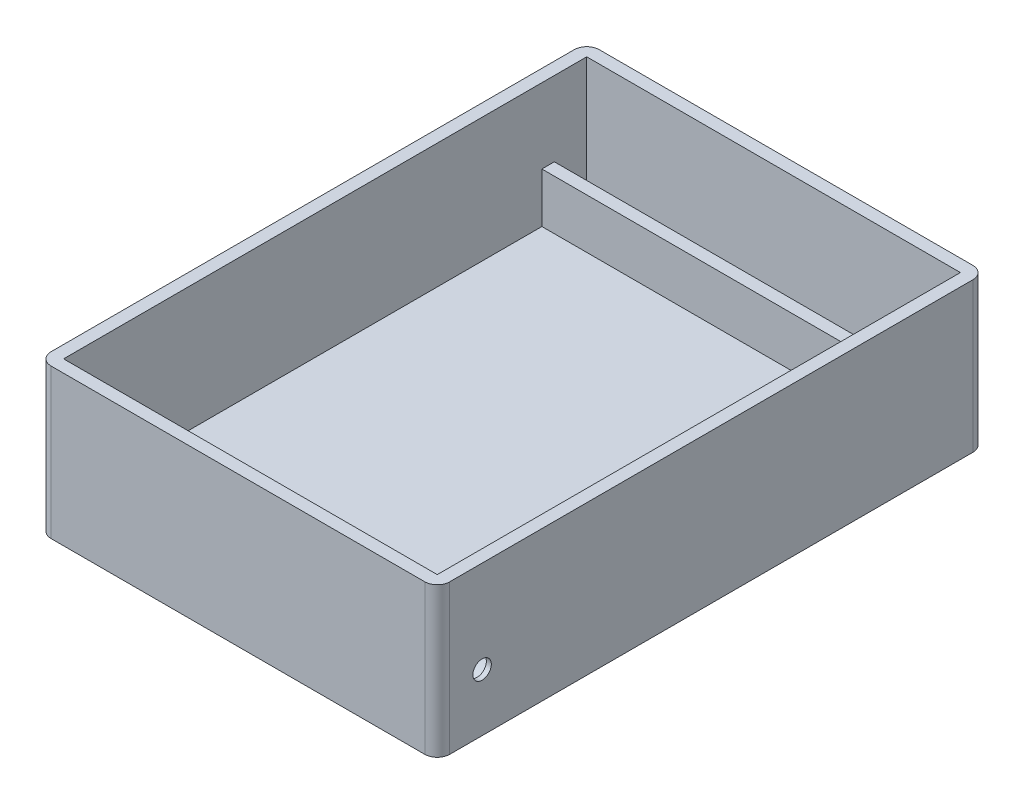
SolidWorks part; units mm, degrees
ref_plane "Front Plane" through (0, 0, 0) normal (0, 0, 1) x (1, 0, 0)
ref_plane "Top Plane" through (0, 0, 0) normal (0, 1, 0) x (1, 0, 0)
ref_plane "Right Plane" through (0, 0, 0) normal (1, 0, 0) x (0, 0, -1)
sketch "Main Body" plane through (0, 0, 0) normal (0, 1, 0) x (1, 0, 0)
  line L0 (-75, 110) -> (75, 110)
  line L1 (-75, -105) -> (75, -105)
  line L2 (-75, -105) -> (-75, 105)
  line L3 (-75, 105) -> (75, 105)
  line L4 (75, -105) -> (75, 105)
  line L5 (-75, -105) -> (75, 105) construction
  line L6 (-75, 105) -> (75, -105) construction
  line L7 (80, -105) -> (80, 105)
  line L8 (-75, -110) -> (75, -110)
  line L9 (-80, -105) -> (-80, 105)
  line L10 (-80, -110) -> (80, -110) construction
  line L11 (-80, -110) -> (-80, 110) construction
  line L12 (80, -110) -> (80, 110) construction
  line L13 (-80, 110) -> (80, 110) construction
  arc A0 (-75, -110) -> (-80, -105) centre (-75, -105) cw
  arc A1 (80, -105) -> (75, -110) centre (75, -105) cw
  arc A2 (75, 110) -> (80, 105) centre (75, 105) cw
  arc A3 (-75, 110) -> (-80, 105) centre (-75, 105) ccw
  point P0 (0, 0)
  dimension "D4" = 5
  dimension "D1" = 75
  dimension "D2" = 210
  dimension "D3" = 5
extrude "Boss-Extrude1" add sketch "Main Body" along normal blind 10 contours L1 L4 L3 L2 | L9 L8 L7 L0 L4 L1 L2 L3 region at (0, 0, -107.2797) region at (0, 0, 0)
extrude "Boss-Extrude3" add sketch "Main Body<4>" along normal blind 50 from surface starting at face at (0, 10, 0)
sketch "Main Body<4>" plane through (0, 0, 0) normal (0, 1, 0) x (1, 0, 0) same geometry as "Main Body"
sketch "Sketch1" plane through (75, 0, 0) normal (-1, 0, 0) x (0, 0, 1)
  line L0 (105, 60) -> (105, 10) construction
  line L1 (-105, 10) -> (105, 10) construction
  line L2 (79, 17.5) -> (105, 17.5)
  line L3 (79, 10) -> (105, 10)
  line L4 (79, 10) -> (79, 36)
  line L5 (79, 36) -> (105, 36)
  line L6 (105, 10) -> (105, 36)
  line L7 (79, 10) -> (105, 36) construction
  line L8 (79, 36) -> (105, 10) construction
  circle A0 centre (92, 23) radius 13
  line M2 (-105, 10) -> (105, 10)
  line M3 (105, 10) -> (105, 60)
  dimension "D1" = 26
  dimension "D2" = 7.5
extrude "Boss-Extrude4" add sketch "Sketch1" along normal up to surface (150 mm away) contours A0 L4 M2 | A0 L3 M3 region at (75, 12.5201, 82.0674) region at (75, 12.5201, 101.9326) up to face at (-75, 35, 0)
sketch "Sketch2" plane through (0, 0, 0) normal (1, 0, 0) x (0, 0, -1)
  line L0 (-105, 60) -> (-105, 17.5) construction
  line L1 (-105, 10) -> (-79, 10)
  line L2 (-105, 10) -> (-105, 17.5)
  line L3 (-105, 17.5) -> (-79, 17.5)
  line L4 (-79, 10) -> (-79, 17.5)
  line L5 (105, 10) -> (-79, 10) construction
  line L6 (-79, 10) -> (-79, 17.5) construction
  line L7 (-79, 17.5) -> (-80.2208, 17.5) construction
extrude "Cut-Extrude1" cut sketch "Sketch2" against normal mid plane 12
sketch "Sketch3" plane through (0, 10, 0) normal (0, 1, 0) x (1, 0, 0)
  line L0 (75, -105) -> (-75, -105) construction
  line L1 (-6, -79) -> (-11, -79)
  line L2 (-6, -79) -> (-6, -105)
  line L3 (-6, -105) -> (-11, -105)
  line L4 (-11, -79) -> (-11, -105)
  line L5 (0, 0) -> (0, -105) construction
  line L6 (-75, -79) -> (-6, -79) construction
  line L7 (11, -79) -> (11, -105)
  line L8 (6, -105) -> (11, -105)
  line L9 (6, -79) -> (6, -105)
  line L10 (6, -79) -> (11, -79)
  dimension "D1" = 5
extrude "Boss-Extrude5" add sketch "Sketch3" along normal up to surface (7.5 mm away) up to face at (40.5, 17.5, 79.6104)
sketch "Sketch4" plane through (0, 10, 0) normal (0, 1, 0) x (1, 0, 0)
  line L0 (-75, -105) -> (-75, 105) construction
  line L1 (-75, 92) -> (75, 92)
  line L2 (-75, 92) -> (-75, 87)
  line L3 (-75, 87) -> (75, 87)
  line L4 (75, 92) -> (75, 87)
  line L5 (75, 105) -> (75, -105) construction
  line L6 (-75, 105) -> (75, 105) construction
  point P10 (75, 91.3674)
  dimension "D1" = 18
  dimension "D2" = 5
extrude "Boss-Extrude6" add sketch "Sketch4" along normal blind 20
sketch "Sketch5" plane through (80, 0, 0) normal (1, 0, 0) x (0, 0, -1)
  circle A0 centre (-92, 23) radius 3.5 construction
  circle A1 centre (-92, 23) radius 3.5
  circle A2 centre (-92, 23) radius 3.7
  dimension "D1" = 0.2
extrude "Cut-Extrude4" cut sketch "Sketch5" against normal up to next contours A1 | A2 A1 region at (80, 23, 92) region at (80, 23, 95.5953)
sketch "Sketch6" plane through (-75, 0, 0) normal (1, 0, 0) x (0, 0, -1)
  circle A0 centre (-92, 23) radius 13
  dimension "D1" = 26
extrude "Cut-Extrude5" cut sketch "Sketch6" against normal offset from surface (3 mm away) 2 up to face at (-80, 30, 0)
mirror "Mirror1" about plane through (0, 0, 0) normal (1, 0, 0) of "Cut-Extrude4"
sketch "Sketch8" plane through (75, 0, 0) normal (-1, 0, 0) x (0, 0, 1)
  circle A0 centre (92, 23) radius 13
  dimension "D1" = 26
extrude "Cut-Extrude6" cut sketch "Sketch8" against normal offset from surface (3 mm away) 2 up to face at (80, 23, 88.3)
